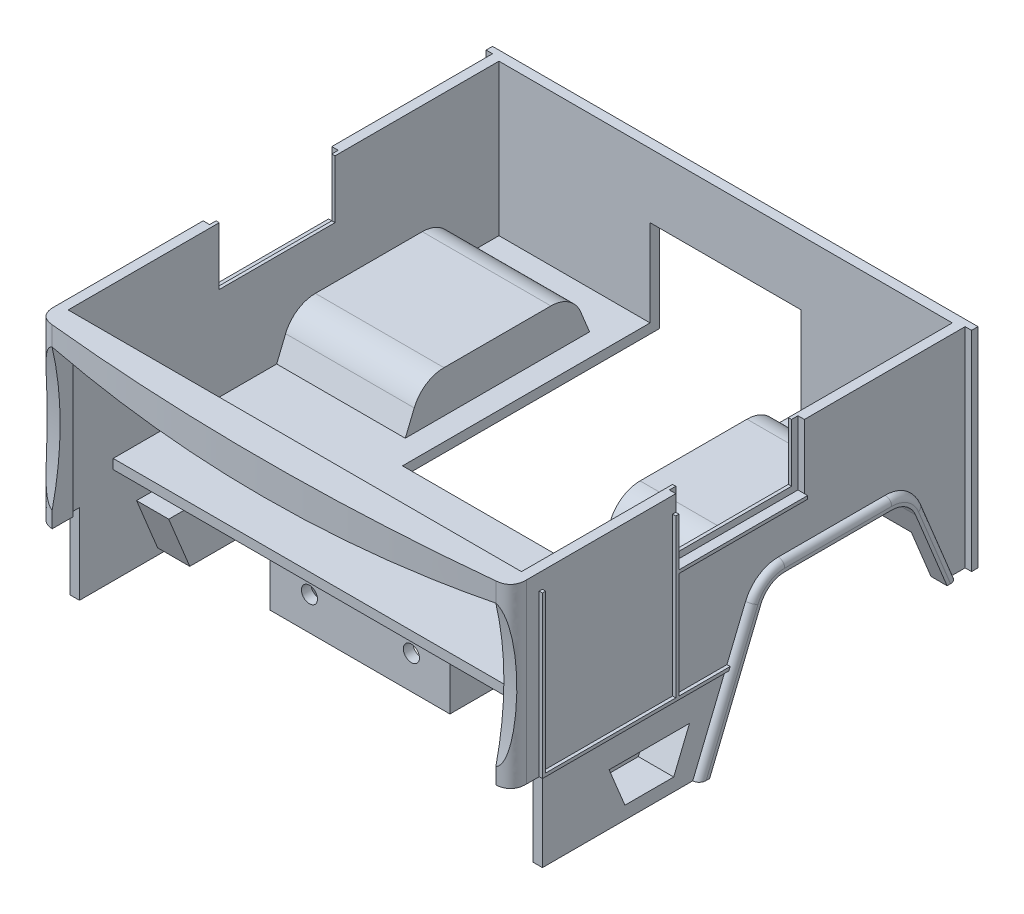
SolidWorks part; units mm, degrees
ref_plane "Front Plane" through (0, 0, 0) normal (0, 0, 1) x (1, 0, 0)
ref_plane "Top Plane" through (0, 0, 0) normal (0, 1, 0) x (1, 0, 0)
ref_plane "Right Plane" through (0, 0, 0) normal (1, 0, 0) x (0, 0, -1)
sketch "Sketch1" plane through (0, 0, 0) normal (0, 1, 0) x (1, 0, 0)
  line L1 (-70.5, 3) -> (70.5, 3)
  line L2 (-73.5, 3) -> (-73.5, -3)
  line L4 (73.5, 3) -> (73.5, -3)
  line L5 (-73.5, 3) -> (73.5, -3) construction
  line L6 (-73.5, -3) -> (73.5, 3) construction
  line L12 (-73.5, 3) -> (-73.5, 140)
  line L13 (-73.5, 140) -> (73.5, 140)
  line L14 (73.5, 140) -> (73.5, 3)
  line L15 (-70.5, 3) -> (-70.5, 137)
  line L16 (-70.5, 137) -> (70.5, 137)
  line L17 (70.5, 137) -> (70.5, 3)
  arc A0 (-73.5, -3) -> (73.5, -3) centre (0, 670.2812) ccw
  point P0 (0, 0)
  point P9 (0, 140)
  point P10 (0, -7)
  point P11 (0, 3)
  dimension "D1" = 6
  dimension "D2" = 147
  dimension "D3" = 147
  dimension "D4" = 147
  dimension "D5" = 10
  dimension "D6" = 6
  dimension "D7" = 6
  dimension "D8" = 3
  dimension "D9" = 3
  dimension "D10" = 3
  dimension "D11" = 3
extrude "Boss-Extrude1" add sketch "Sketch1" along normal blind 55
fillet "Fillet1" radius 5 2 edges at (73.5, 27.5, 3) (-73.5, 27.5, 3) conic rho 0.5
ref_plane "Plane2" through (0, 0, 10) normal (0, 0, 1) x (1, 0, 0)
sketch "Sketch2" plane through (0, 0, 10) normal (0, 0, 1) x (1, 0, 0)
  line L0 (-69.0095, 55) -> (-69.0095, 0) construction
  line L2 (-69.0095, 49) -> (-69.0095, 0)
  line L3 (-69.0095, 0) -> (69.0095, 0)
  line L4 (69.0095, 49) -> (69.0095, 0)
  line L5 (69.0095, 55) -> (-69.0095, 55) construction
  arc A0 (-69.0095, 49) -> (69.0095, 49) centre (0, 642.2882) ccw
  point P11 (0, 55)
  point P12 (0, 45)
  dimension "D1" = 6
  dimension "D2" = 10
  dimension "D3" = 49
extrude "Cut-Extrude1" cut sketch "Sketch2" against normal up to surface (13 mm away) and the other way through all up to face at (0, 27.5, -3)
sketch "Sketch6" plane through (-73.5, 0, 0) normal (-1, 0, 0) x (0, 0, 1)
  line L0 (3.4751, 49) -> (3.4751, 0) construction
  line L1 (3.4751, 49) -> (3.4751, 5)
  arc A0 (3.4751, 49) -> (3.4751, 5) centre (99.0251, 27) ccw
  point P4 (0.9751, 27)
  point P5 (3.4751, 27)
  dimension "D1" = 5
  dimension "D2" = 2.5
extrude "Cut-Extrude2" cut sketch "Sketch6" against normal through all
sketch "Sketch7" plane through (0, 0, 0) normal (0, -1, 0) x (1, 0, 0)
  line L0 (-73.5, -6.5249) -> (-73.5, -140)
  line L1 (-73.5, -140) -> (-73.5, -1.4989) construction
  line L2 (-73.5, -140) -> (73.5, -140)
  line L3 (73.5, -140) -> (73.5, -6.5249)
  line L4 (73.5, -1.4989) -> (73.5, -140) construction
  line L5 (-69.0095, 3.4751) -> (69.0095, 3.4751) construction
  line L6 (-73.5, -6.5249) -> (-70.5, -6.5249)
  line L7 (-70.5, -137) -> (-70.5, -3) construction
  line L8 (-70.5, -6.5249) -> (-70.5, -137)
  line L9 (-70.5, -137) -> (70.5, -137)
  line L10 (70.5, -137) -> (70.5, -6.5249)
  line L11 (70.5, -3) -> (70.5, -137) construction
  line L12 (70.5, -6.5249) -> (73.5, -6.5249)
  dimension "D1" = 10
  dimension "D2" = 10
extrude "Boss-Extrude2" add sketch "Sketch7" along normal blind 25
sketch "Sketch8" plane through (73.5, 0, 0) normal (1, 0, 0) x (0, 0, -1)
  line L0 (140, -25) -> (6.5249, -25) construction
  line L1 (140, 55) -> (138, 55)
  line L2 (140, 55) -> (140, -25)
  line L3 (140, -25) -> (138, -25)
  line L4 (138, 55) -> (138, -25)
  dimension "D1" = 2
  dimension "D2" = 80
extrude "Boss-Extrude3" add sketch "Sketch8" along normal blind 2
mirror "Mirror1" about plane through (0, 0, 0) normal (1, 0, 0) of "Boss-Extrude3"
sketch "Sketch9" plane through (73.5, 0, 0) normal (1, 0, 0) x (0, 0, -1)
  line L0 (56.5249, -25) -> (136.5249, -25)
  line L1 (138, -25) -> (6.5249, -25) construction
  line L2 (130.3886, -10) -> (120.5585, 14.0291)
  line L3 (113.1541, 19) -> (79.8957, 19)
  line L4 (72.4914, 14.0291) -> (56.5249, -25)
  line L5 (96.5249, -25) -> (96.5249, 40.7342) construction
  line L6 (130.3886, -10) -> (140, -10)
  line L7 (140, -25) -> (140, 55) construction
  line L8 (136.5249, -25) -> (140, -25)
  line L9 (140, -25) -> (140, -10)
  line L10 (1.4989, 55) -> (138, 55) construction
  line L11 (88, 55) -> (48, 55)
  line L12 (88, 55) -> (88, 35)
  line L13 (88, 35) -> (48, 35)
  line L14 (48, 55) -> (48, 35)
  line L17 (47.3569, -21) -> (32.176, -21)
  line L19 (27.266, -9) -> (52.266, -9)
  line L20 (52.266, -9) -> (47.3569, -21)
  line L21 (27.266, -9) -> (32.176, -21)
  line L22 (39.766, -9) -> (39.766, -34.9886) construction
  arc A0 (79.8957, 19) -> (72.4914, 14.0291) centre (79.8957, 11) ccw
  arc A1 (120.5585, 14.0291) -> (113.1541, 19) centre (113.1541, 11) ccw
  point P29 (0, 0)
  point P32 (74.5249, 19)
  point P35 (118.5249, 19)
  dimension "D16" = 8
  dimension "D1" = 80
  dimension "D2" = 60
  dimension "D3" = 44
  dimension "D4" = 44
  dimension "D5" = 22
  dimension "D6" = 15
  dimension "D7" = 40
  dimension "D8" = 50
  dimension "D9" = 20
  dimension "D10" = 4
  dimension "D11" = 12
  dimension "D12" = 25
  dimension "D13" = 7.5909
  dimension "D14" = 10
  dimension "D15" = 7.59
extrude "Cut-Extrude3" cut sketch "Sketch9" against normal through all both and the other way through all
sketch "Sketch10" plane through (73.5, 0, 0) normal (1, 0, 0) x (0, 0, -1)
  line L9 (56.5249, -25) -> (72.4914, 14.0291) construction
  line L11 (79.8957, 19) -> (113.1541, 19) construction
  line L28 (120.5585, 14.0291) -> (130.3886, -10) construction
  line L29 (56.5249, -25) -> (72.4914, 14.0291)
  line L30 (79.8957, 19) -> (113.1541, 19)
  line L31 (120.5585, 14.0291) -> (130.3886, -10)
  line L32 (69.7147, 15.165) -> (53.2836, -25)
  line L33 (79.8957, 22) -> (113.1541, 22)
  line L34 (123.3351, 15.165) -> (133.6299, -10)
  line L35 (53.7483, -23.8641) -> (69.7147, 15.165) construction
  line L36 (123.3351, 15.165) -> (133.1652, -8.8641) construction
  line L37 (56.5249, -25) -> (6.5249, -25) construction
  line L38 (56.5249, -25) -> (53.2836, -25)
  line L39 (130.3886, -10) -> (138, -10) construction
  line L40 (130.3886, -10) -> (133.6299, -10)
  arc A4 (79.8957, 19) -> (72.4914, 14.0291) centre (79.8957, 11) ccw construction
  arc A5 (120.5585, 14.0291) -> (113.1541, 19) centre (113.1541, 11) ccw construction
  arc A6 (79.8957, 19) -> (72.4914, 14.0291) centre (79.8957, 11) ccw
  arc A7 (120.5585, 14.0291) -> (113.1541, 19) centre (113.1541, 11) ccw
  arc A8 (79.8957, 22) -> (69.7147, 15.165) centre (79.8957, 11) ccw
  arc A9 (123.3351, 15.165) -> (113.1541, 22) centre (113.1541, 11) ccw
  dimension "D2" = 3
  dimension "D3" = 3
  dimension "D1" = 3
extrude "Boss-Extrude4" add sketch "Sketch10" along normal blind 2
mirror "Mirror2" about plane through (0, 0, 0) normal (1, 0, 0) of "Boss-Extrude4"
sketch "Sketch11" plane through (70.5, 0, 0) normal (-1, 0, 0) x (0, 0, 1)
  line L0 (-27.266, -9) -> (-52.266, -9) construction
  line L1 (-27.266, -9) -> (-52.266, -9)
  line L2 (-52.266, -9) -> (-47.3569, -21) construction
  line L3 (-52.266, -9) -> (-47.3569, -21)
  line L4 (-47.3569, -21) -> (-32.176, -21) construction
  line L5 (-47.3569, -21) -> (-32.176, -21)
  line L6 (-32.176, -21) -> (-27.266, -9) construction
  line L7 (-32.176, -21) -> (-27.266, -9)
  line L8 (-24.2867, -7) -> (-55.245, -7)
  line L9 (-55.245, -7) -> (-48.6996, -23)
  line L10 (-48.6996, -23) -> (-30.8333, -23)
  line L11 (-30.8333, -23) -> (-24.2867, -7)
  dimension "D1" = 2
extrude "Boss-Extrude5" add sketch "Sketch11" along normal blind 10
sketch "Sketch12" plane through (60.5, 0, 0) normal (-1, 0, 0) x (0, 0, 1)
  line L0 (-27.266, -9) -> (-52.266, -9) construction
  line L1 (-27.266, -9) -> (-52.266, -9)
  line L2 (-52.266, -9) -> (-47.3569, -21) construction
  line L3 (-52.266, -9) -> (-47.3569, -21)
  line L4 (-47.3569, -21) -> (-32.176, -21) construction
  line L5 (-47.3569, -21) -> (-32.176, -21)
  line L6 (-32.176, -21) -> (-27.266, -9) construction
  line L7 (-32.176, -21) -> (-27.266, -9)
extrude "Boss-Extrude6" add sketch "Sketch12" against normal blind 2
mirror "Mirror3" about plane through (0, 0, 0) normal (1, 0, 0) of "Boss-Extrude5", "Boss-Extrude6"
sketch "Sketch14" plane through (70.5, 0, 0) normal (-1, 0, 0) x (0, 0, 1)
  line L0 (-48, 35) -> (-48, 55) construction
  line L1 (-88, 35) -> (-48, 35) construction
  line L2 (-88, 55) -> (-88, 35) construction
  line L3 (-48, 35) -> (-48, 55)
  line L4 (-88, 35) -> (-48, 35)
  line L5 (-88, 55) -> (-88, 35)
  line L6 (-86, 55) -> (-86, 37)
  line L7 (-86, 37) -> (-50, 37)
  line L8 (-50, 37) -> (-50, 55)
  line L9 (-88, 55) -> (-86, 55)
  line L10 (-48, 55) -> (-50, 55)
  dimension "D1" = 2
extrude "Boss-Extrude7" add sketch "Sketch14" against normal blind 1
mirror "Mirror4" about plane through (0, 0, 0) normal (1, 0, 0) of "Boss-Extrude7"
sketch "Sketch15" plane through (0, 0, -137) normal (0, 0, 1) x (1, 0, 0)
  line L0 (-70.5, 55) -> (-70.5, -10) construction
  line L1 (-70.5, 8) -> (70.5, 8)
  line L2 (-70.5, 8) -> (-70.5, 5)
  line L3 (-70.5, 5) -> (70.5, 5)
  line L4 (70.5, 8) -> (70.5, 5)
  line L5 (70.5, 55) -> (70.5, -10) construction
  line L6 (70.5, -10) -> (-70.5, -10) construction
  dimension "D1" = 3
  dimension "D2" = 15
extrude "Boss-Extrude8" add sketch "Sketch15" along normal blind 120
fillet "Fillet4" radius 2 5 edges at (75.5, 2.5825, -128.4825) (75.5, 20.1328, -119.2854) (75.5, 22, -96.5249) (75.5, 20.1328, -73.7644) (75.5, -4.9175, -61.4992)
fillet "Fillet5" radius 2 5 edges at (-75.5, 2.5825, -128.4825) (-75.5, -4.9175, -61.4992) (-75.5, 20.1328, -73.7644) (-75.5, 22, -96.5249) (-75.5, 20.1328, -119.2854)
sketch "Sketch16" plane through (70.5, 0, 0) normal (-1, 0, 0) x (0, 0, 1)
  line L0 (-70.0249, 8) -> (-72.4914, 14.0291) construction
  line L1 (-79.8957, 19) -> (-113.1541, 19) construction
  line L2 (-120.5585, 14.0291) -> (-123.0249, 8) construction
  line L3 (-70.0249, 8) -> (-72.4914, 14.0291)
  line L4 (-79.8957, 19) -> (-113.1541, 19)
  line L5 (-120.5585, 14.0291) -> (-123.0249, 8)
  line L6 (-123.0249, 8) -> (-137, 8) construction
  line L7 (-123.0249, 8) -> (-125.1858, 8)
  line L8 (-17, 8) -> (-70.0249, 8) construction
  line L9 (-67.864, 8) -> (-70.0249, 8)
  line L10 (-122.4096, 14.7863) -> (-125.1858, 8)
  line L11 (-79.8957, 21) -> (-113.1541, 21)
  line L12 (-70.6403, 14.7863) -> (-67.864, 8)
  line L13 (-122.4096, 14.7863) -> (-124.876, 8.7573) construction
  line L14 (-68.1738, 8.7573) -> (-70.6403, 14.7863) construction
  arc A0 (-72.4914, 14.0291) -> (-79.8957, 19) centre (-79.8957, 11) ccw construction
  arc A1 (-113.1541, 19) -> (-120.5585, 14.0291) centre (-113.1541, 11) ccw construction
  arc A2 (-72.4914, 14.0291) -> (-79.8957, 19) centre (-79.8957, 11) ccw
  arc A3 (-113.1541, 19) -> (-120.5585, 14.0291) centre (-113.1541, 11) ccw
  arc A4 (-70.6403, 14.7863) -> (-79.8957, 21) centre (-79.8957, 11) ccw
  arc A5 (-113.1541, 21) -> (-122.4096, 14.7863) centre (-113.1541, 11) ccw
  dimension "D1" = 2
extrude "Boss-Extrude9" add sketch "Sketch16" along normal blind 40
sketch "Sketch17" plane through (30.5, 0, 0) normal (-1, 0, 0) x (0, 0, 1)
  line L0 (-125.1858, 8) -> (-67.864, 8)
  line L1 (-67.864, 8) -> (-70.6403, 14.7863) construction
  line L2 (-79.8957, 21) -> (-113.1541, 21) construction
  line L3 (-122.4096, 14.7863) -> (-125.1858, 8) construction
  line L4 (-67.864, 8) -> (-70.6403, 14.7863)
  line L5 (-79.8957, 21) -> (-113.1541, 21)
  line L6 (-122.4096, 14.7863) -> (-125.1858, 8)
  arc A0 (-70.6403, 14.7863) -> (-79.8957, 21) centre (-79.8957, 11) ccw construction
  arc A1 (-113.1541, 21) -> (-122.4096, 14.7863) centre (-113.1541, 11) ccw construction
  arc A2 (-70.6403, 14.7863) -> (-79.8957, 21) centre (-79.8957, 11) ccw
  arc A3 (-113.1541, 21) -> (-122.4096, 14.7863) centre (-113.1541, 11) ccw
extrude "Boss-Extrude10" add sketch "Sketch17" against normal blind 2
sketch "Sketch18" plane through (70.5, 0, 0) normal (1, 0, 0) x (0, 0, -1)
  line L4 (68.7977, 5) -> (124.2522, 5)
  line L5 (124.2522, 5) -> (123.0249, 8)
  line L6 (123.0249, 8) -> (70.0249, 8)
  line L7 (70.0249, 8) -> (68.7977, 5)
  line L8 (68.7977, 5) -> (124.2522, 5)
  line L9 (124.2522, 5) -> (123.0249, 8)
  line L10 (123.0249, 8) -> (70.0249, 8)
  line L11 (70.0249, 8) -> (68.7977, 5)
  dimension "D1" = 0
extrude "Cut-Extrude4" cut sketch "Sketch18" against normal up to surface (38 mm away) up to face at (32.5, 14.0522, -96.5249)
mirror "Mirror5" about plane through (0, 0, 0) normal (1, 0, 0) of "Cut-Extrude4", "Boss-Extrude10", "Boss-Extrude9"
sketch "Sketch19" plane through (0, 0, -137) normal (0, 0, 1) x (1, 0, 0)
  line L0 (-70.5, 5) -> (70.5, 5) construction
  line L1 (-60.5, 5) -> (60.5, 5)
  line L2 (-60.5, 5) -> (-60.5, -10)
  line L3 (-60.5, -10) -> (60.5, -10)
  line L4 (60.5, 5) -> (60.5, -10)
  line L5 (70.5, -10) -> (-70.5, -10) construction
  dimension "D1" = 10
  dimension "D2" = 10
extrude "Cut-Extrude5" cut sketch "Sketch19" against normal up to surface (3 mm away) up to face at (0, 22.5, -140)
sketch "Sketch20" plane through (0, 0, -140) normal (0, 0, -1) x (-1, 0, 0)
  line L0 (0, 55) -> (0, -40.0291) construction
  line L1 (-75.5, 55) -> (75.5, 55) construction
  line L2 (60.5, 5) -> (-60.5, 5) construction
  line L3 (-23.5, 5) -> (23.5, 5)
  line L4 (-23.5, 5) -> (-23.5, 35)
  line L5 (-23.5, 35) -> (23.5, 35)
  line L6 (23.5, 5) -> (23.5, 35)
  dimension "D1" = 30
  dimension "D2" = 47
  dimension "D3" = 23.5
extrude "Cut-Extrude6" cut sketch "Sketch20" against normal blind 80
sketch "Sketch21" plane through (0, 5, 0) normal (0, -1, 0) x (1, 0, 0)
  line L0 (32.5, -68.7977) -> (32.5, -124.2522) construction
  line L1 (-28.2715, -23.5249) -> (27.7285, -23.5249)
  line L3 (-24.5595, -26.5249) -> (24.0991, -26.5249)
  line L5 (-28.2715, -23.5249) -> (-28.2715, -53.5249)
  line L6 (-28.2715, -53.5249) -> (-24.5595, -53.5249)
  line L7 (-24.5595, -53.5249) -> (-24.5595, -26.5249)
  line L8 (27.7285, -23.5249) -> (27.7285, -53.5249)
  line L9 (27.7285, -53.5249) -> (24.0991, -53.5249)
  line L10 (24.0991, -53.5249) -> (24.0991, -26.5249)
  point P6 (32.5, -96.5249)
  dimension "D1" = 70
  dimension "D2" = 56
  dimension "D4" = 30
  dimension "D5" = 30
extrude "Boss-Extrude11" add sketch "Sketch21" along normal blind 20
sketch "Sketch22" plane through (0, 0, -26.5249) normal (0, 0, -1) x (-1, 0, 0)
  line L0 (-23.5, 5) -> (23.5, 5) construction
  line L1 (24.5595, 5) -> (-24.0991, 5) construction
  line L2 (0, 5) -> (0.2302, -15) construction
  line L3 (24.5595, -15) -> (-24.0991, -15) construction
  circle A0 centre (-15.7379, -4.65) radius 2.5
  circle A1 centre (15.9621, -4.65) radius 2.5
  dimension "D1" = 5
  dimension "D2" = 5
  dimension "D3" = 9.65
  dimension "D4" = 9.65
  dimension "D5" = 31.7
  dimension "D6" = 15.85
  dimension "D7" = 15.8479
extrude "Cut-Extrude7" cut sketch "Sketch22" against normal blind 20
sketch "Sketch23" plane through (73.5, 0, 0) normal (1, 0, 0) x (0, 0, -1)
  line L5 (1.4989, 55) -> (48, 55) construction
  line L6 (6.5249, 0) -> (5.5249, 0)
  line L7 (6.5249, 1) -> (6.5249, 50)
  line L8 (6.5249, 50) -> (5.5249, 50)
  line L9 (5.5249, 0) -> (5.5249, 50)
  line L10 (69.7147, 15.165) -> (53.2836, -25) construction
  line L11 (6.5249, 1) -> (47, 1)
  line L13 (6.5249, 0) -> (63.5109, 0)
  line L15 (63.92, 1) -> (63.5109, 0)
  line L16 (48, 35) -> (48, 55) construction
  line L17 (48, 50) -> (47, 50)
  line L18 (48, 50) -> (48, 35)
  line L20 (47, 50) -> (47, 1)
  line L21 (48, 1) -> (63.92, 1)
  line L22 (88, 55) -> (88, 35) construction
  line L23 (48, 35) -> (88, 35)
  line L25 (48, 34) -> (88, 34)
  line L26 (88, 35) -> (88, 34)
  line L27 (48, 34) -> (48, 1)
  dimension "D1" = 5
  dimension "D2" = 1
  dimension "D3" = 1
  dimension "D4" = 1
extrude "Boss-Extrude12" add sketch "Sketch23" along normal blind 1
mirror "Mirror6" about plane through (0, 0, 0) normal (1, 0, 0) of "Boss-Extrude12"
